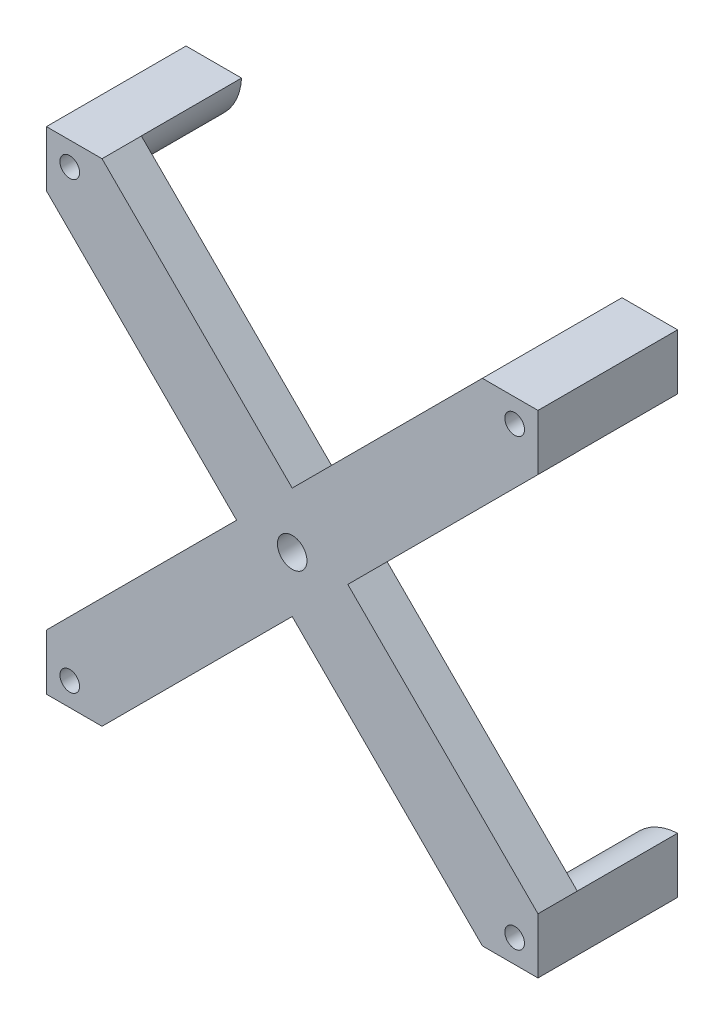
SolidWorks part; units mm, degrees
ref_plane "Front Plane" through (0, 0, 0) normal (0, 0, 1) x (1, 0, 0)
ref_plane "Top Plane" through (0, 0, 0) normal (0, 1, 0) x (1, 0, 0)
ref_plane "Right Plane" through (0, 0, 0) normal (1, 0, 0) x (0, 0, -1)
sketch "Sketch1" plane through (0, 0, 0) normal (0, 0, 1) x (1, 0, 0)
  line L1 (-25, -25) -> (25, -25)
  line L2 (-25, -25) -> (-25, 25)
  line L3 (-25, 25) -> (25, 25)
  line L4 (25, -25) -> (25, 25)
  line L5 (-25, -25) -> (25, 25) construction
  line L6 (-25, 25) -> (25, -25) construction
  circle A0 centre (-22.6274, 22.6274) radius 1
  circle A1 centre (22.6274, 22.6274) radius 1
  circle A2 centre (22.6274, -22.6274) radius 1
  circle A3 centre (-22.6274, -22.6274) radius 1
  point P0 (0, 0)
  dimension "D3" = 2
  dimension "D4" = 32
  dimension "D5" = 2
  dimension "D6" = 2
  dimension "D7" = 2
  dimension "D8" = 32
  dimension "D9" = 32
  dimension "D10" = 32
  dimension "D1" = 50
  dimension "D2" = 50
extrude "Boss-Extrude1" add sketch "Sketch1" along normal blind 4
sketch "Sketch2" plane through (0, 0, 4) normal (0, 0, 1) x (1, 0, 0)
  line L0 (-22.6274, 22.6274) -> (22.6274, -22.6274)
  line L1 (22.6274, 22.6274) -> (-22.6274, -22.6274)
  line L2 (-25, 19.3431) -> (-5.6569, 0)
  line L3 (-25, 25) -> (-25, -25) construction
  line L4 (-5.6569, 0) -> (-25, -19.3431)
  line L5 (19.3431, 25) -> (0, 5.6569)
  line L6 (0, 5.6569) -> (-19.3431, 25)
  line L7 (25, -19.3431) -> (5.6569, 0)
  line L8 (5.6569, 0) -> (25, 19.3431)
  line L9 (-19.3431, -25) -> (0, -5.6569)
  line L10 (0, -5.6569) -> (19.3431, -25)
  circle A0 centre (0, 0) radius 1.5
  point P28 (0, 0)
  line M7 (25, -25) -> (25, 25)
  line M8 (25, 25) -> (-25, 25)
  line M9 (-25, 25) -> (-25, -25)
  line M10 (-25, -25) -> (25, -25)
  dimension "D1" = 3
  dimension "D2" = 4
  dimension "D3" = 4
  dimension "D4" = 4
extrude "Cut-Extrude1" cut sketch "Sketch2" against normal blind 10 contours L4 L2 M9 | L6 L5 M8 | L8 L7 M7 | L10 L9 M10 | L1 A0 L0 | L0 A0 L1 | L1 A0 L0 | L0 A0 L1 region at (0, 0.9003, 4) region at (-0.9003, 0, 4) region at (0.9003, 0, 4) region at (0, -0.9003, 4) region at (-18.5523, 0, 4) region at (0, 18.5523, 4) region at (0, -18.5523, 4) region at (18.5523, 0, 4)
sketch "Sketch3" plane through (0, 0, 0) normal (0, 0, -1) x (-1, 0, 0)
  line L0 (25, 25) -> (19.3431, 25)
  line L1 (-25, 25) -> (-19.3431, 25)
  line L2 (-25, 25) -> (-25, 19.3431)
  line L3 (-25, 19.3431) -> (-19.3431, 19.3431)
  line L4 (-19.3431, 25) -> (-19.3431, 19.3431)
  line L5 (25, 25) -> (25, 19.3431)
  line L6 (25, 19.3431) -> (19.3431, 19.3431)
  line L7 (19.3431, 25) -> (19.3431, 19.3431)
  line L8 (25, -25) -> (25, -19.3431)
  line L9 (25, -25) -> (19.3431, -25)
  line L10 (19.3431, -25) -> (19.3431, -19.3431)
  line L11 (25, -19.3431) -> (19.3431, -19.3431)
  line L12 (-25, -25) -> (-19.3431, -25)
  line L13 (-25, -25) -> (-25, -19.3431)
  line L14 (-25, -19.3431) -> (-19.3431, -19.3431)
  line L15 (-19.3431, -25) -> (-19.3431, -19.3431)
  circle A0 centre (-22.6274, 22.6274) radius 1
  circle A1 centre (22.6274, 22.6274) radius 1
  circle A2 centre (22.6274, -22.6274) radius 1
  circle A3 centre (-22.6274, -22.6274) radius 1
  point P31 (0, 0)
  dimension "D1" = 2
  dimension "D2" = 4
extrude "Boss-Extrude2" add sketch "Sketch3" along normal blind 10.2
fillet "Fillet1" radius 6 4 edges at (19.3431, -19.3431, -5.1) (-19.3431, -19.3431, -5.1) (19.3431, 19.3431, -5.1) (-19.3431, 19.3431, -5.1)
